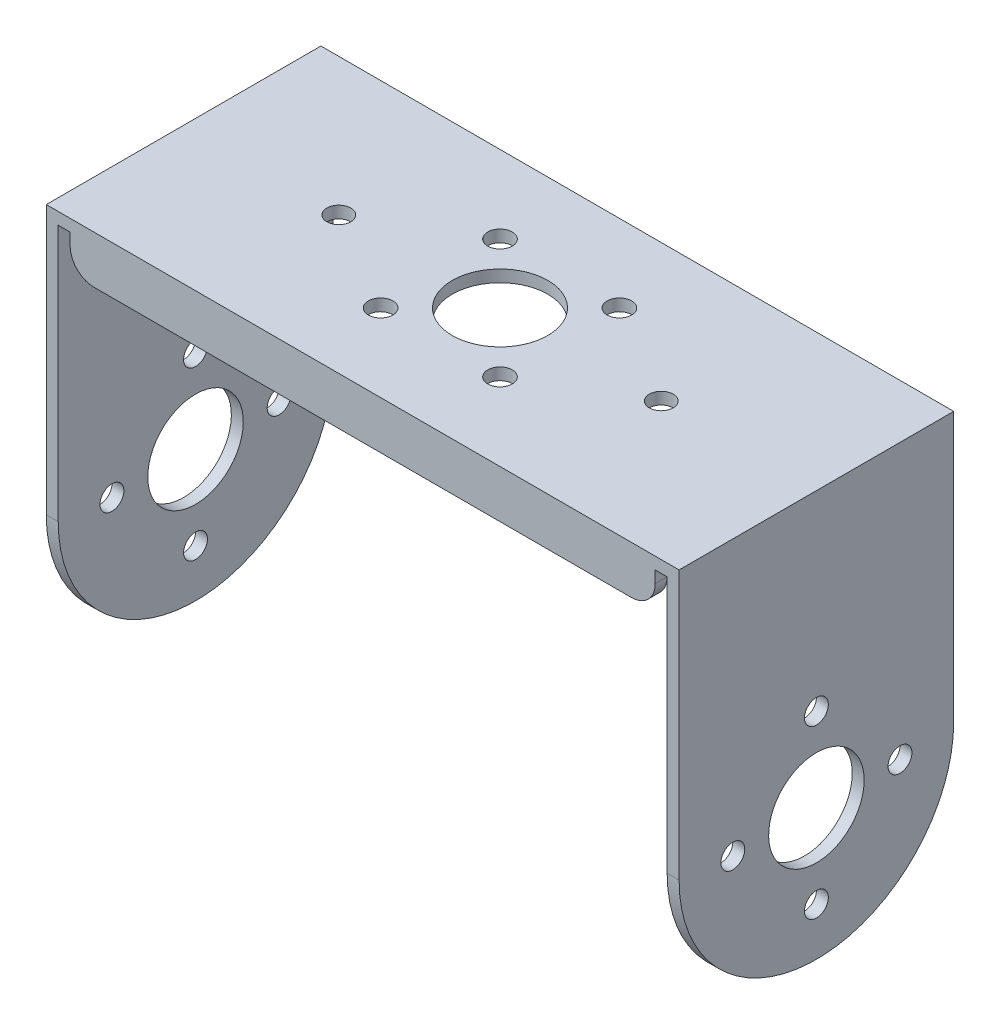
SolidWorks part; units mm, degrees
ref_plane "前视基准面" through (0, 0, 0) normal (0, 0, 1) x (1, 0, 0)
ref_plane "上视基准面" through (0, 0, 0) normal (0, 1, 0) x (1, 0, 0)
ref_plane "右视基准面" through (0, 0, 0) normal (1, 0, 0) x (0, 0, -1)
sketch "草图1" plane through (0, 0, 0) normal (0, 0, 1) x (1, 0, 0)
  line L0 (-26.5, 1) -> (-26.5, -32)
  line L1 (-26.5, -32) -> (-25.5, -32)
  line L2 (-25.5, -32) -> (-25.5, 0)
  line L3 (-25.5, 0) -> (25.5, 0)
  line L4 (25.5, 0) -> (25.5, -32)
  line L5 (25.5, -32) -> (26.5, -32)
  line L6 (26.5, -32) -> (26.5, 1)
  line L7 (26.5, 1) -> (-26.5, 1)
  dimension "D1" = 1
  dimension "D2" = 1
  dimension "D3" = 32
  dimension "D4" = 33
  dimension "D5" = 51
extrude "凸台-拉伸1" add sketch "草图1" along normal blind 21
sketch "草图2" plane through (-26.5, 0, 0) normal (-1, 0, 0) x (0, 0, 1)
  line L0 (10.5, -48.887) -> (10.5, 0.6402) construction
  line L1 (21, -32) -> (0, -32) construction
  line L5 (0, 1) -> (0, -32) construction
  line L6 (0, -32) -> (10.5, -32)
  line L7 (0, -32) -> (0, -21.5)
  arc A0 (0, -21.5) -> (10.5, -32) centre (10.5, -21.5) ccw
extrude "切除-拉伸1" cut sketch "草图2" against normal up to surface (53 mm away) up to face at (26.5, -15.5, 10.5)
ref_axis "基准轴1" through (-26.5, 1, 10.5) along (1, 0, 0)
ref_plane "基准面1" through (0, 0, 10.5) normal (0, 0, 1) x (1, 0, 0)
mirror "镜向1" about plane through (0, 0, 10.5) normal (0, 0, 1) of "切除-拉伸1"
sketch "草图3" plane through (26.5, 0, 0) normal (1, 0, 0) x (0, 0, -1)
  line L0 (-10.5, -38.5331) -> (-10.5, 10.5786) construction
  line L1 (-10.5, -32) -> (-2.4743, -32) construction
  line L2 (0, -21.5) -> (0, 1) construction
  circle A0 centre (-10.5, -22) radius 4
  circle A1 centre (-3.5, -22) radius 1
  circle A2 centre (-10.5, -15) radius 1
  circle A3 centre (-17.5, -22) radius 1
  circle A4 centre (-10.5, -29) radius 1
  arc A5 (-21, -21.5) -> (0, -21.5) centre (-10.5, -21.5) ccw construction
  dimension "D1" = 2
  dimension "D2" = 8
  dimension "D3" = 10
  dimension "D4" = 7
  dimension "D5" = 7
  dimension "D6" = 7
  dimension "D7" = 7
  dimension "D8" = 10.5
extrude "切除-拉伸2" cut sketch "草图3" against normal up to surface (53 mm away) up to face at (-26.5, -12.875, 10.5)
sketch "草图4" plane through (0, 1, 0) normal (0, 1, 0) x (1, 0, 0)
  line L0 (-29.1776, -10.5) -> (29.4412, -10.5) construction
  line L1 (0, 5.3481) -> (0, -30.3599) construction
  line L2 (26.5, -21) -> (-26.5, -21) construction
  line L3 (-26.5, -21) -> (-26.5, 0) construction
  line L4 (26.5, -21) -> (26.5, 0) construction
  circle A0 centre (0, -10.5) radius 4
  circle A1 centre (5, -5.5) radius 1.0266
  circle A2 centre (13.5, -10.5) radius 1
  circle A3 centre (-13.5, -10.5) radius 1
  circle A4 centre (5, -15.5) radius 1.0266
  circle A5 centre (-5, -5.5) radius 1.0266
  circle A6 centre (-5, -15.5) radius 1.0266
  dimension "D1" = 5
  dimension "D2" = 5
  dimension "D3" = 13.5
  dimension "D4" = 13.5
  dimension "D5" = 5
  dimension "D6" = 5
  dimension "D9" = 10
  dimension "D10" = 10
  dimension "D11" = 10
  dimension "D7" = 58.6188
  dimension "D8" = 10.5
  dimension "D12" = 26.5
  dimension "D13" = 26.5
extrude "切除-拉伸3" cut sketch "草图4" against normal blind 1
sketch "草图6" plane through (0, 0, 21) normal (0, 0, 1) x (1, 0, 0)
  line L0 (24.5, 0) -> (24.5, 1)
  line L1 (-25.5, 0) -> (25.5, 0) construction
  line L2 (26.5, 1) -> (-26.5, 1) construction
  line L3 (24.5, 1) -> (-24.5, 1)
  line L4 (-24.5, 1) -> (-24.5, 0)
  line L5 (-24.5, 0) -> (24.5, 0)
  line L6 (25.5, 0) -> (25.5, -21.5) construction
  line L7 (-25.5, -21.5) -> (-25.5, 0) construction
  dimension "D1" = 1
  dimension "D2" = 1
extrude "凸台-拉伸2" add sketch "草图6" along normal blind 1
sketch "草图7" plane through (0, 0, 0) normal (0, -1, 0) x (1, 0, 0)
  line L0 (24.5, 21) -> (24.5, 22)
  line L1 (24.5, 22) -> (-24.5, 22)
  line L2 (-24.5, 22) -> (-24.5, 21)
  line L3 (-24.5, 21) -> (24.5, 21)
extrude "凸台-拉伸3" add sketch "草图7" along normal blind 3
sketch "草图8" plane through (0, 0, 0) normal (0, -1, 0) x (1, 0, 0)
  line L0 (25.5, 21) -> (24.5, 21)
  line L1 (24.5, 21) -> (24.5, 22)
  arc A0 (24.5, 22) -> (25.5, 21) centre (25.5, 22) ccw
ref_plane "基准面2" through (0, 0, 0) normal (1, 0, 0) x (0, 0, -1)
fillet "圆角1" radius 2 2 edges at (-24.5, -3, 21.5) (24.5, -3, 21.5)
mirror "镜向3" about plane through (0, 0, 10.5) normal (0, 0, 1) of "凸台-拉伸3", "凸台-拉伸2", "圆角1"
sketch "草图9" plane through (26.5, 0, 0) normal (1, 0, 0) x (0, 0, -1)
  line L0 (-21, 1) -> (-22, 1)
  line L1 (-22, 1) -> (-22, -21.5)
  line L2 (0, 1) -> (1, 1)
  line L3 (1, 1) -> (1, -21.5)
  line L4 (-21, -21.5) -> (-21, 1) construction
  line L5 (-21, -21.5) -> (-21, 1)
  line L6 (0, -21.5) -> (0, 1) construction
  line L7 (0, -21.5) -> (0, 1)
  arc A0 (-21, -21.5) -> (0, -21.5) centre (-10.5, -21.5) ccw construction
  arc A1 (-21, -21.5) -> (0, -21.5) centre (-10.5, -21.5) ccw
  arc A2 (-22, -21.5) -> (1, -21.5) centre (-10.5, -21.5) ccw
extrude "凸台-拉伸4" add sketch "草图9" against normal blind 1
mirror "镜向4" about plane through (0, 0, 0) normal (1, 0, 0) of "凸台-拉伸4"
sketch "草图10" plane through (0, 1, 0) normal (0, 1, 0) x (1, 0, 0)
  line L1 (-25.5, 1) -> (-24.5, 1)
  line L2 (-25.5, 1) -> (-25.5, 0)
  line L3 (-25.5, 0) -> (-24.5, 0)
  line L4 (-24.5, 1) -> (-24.5, 0)
  line L5 (-25.5, -21) -> (-24.5, -21)
  line L6 (-25.5, -21) -> (-25.5, -22)
  line L7 (-25.5, -22) -> (-24.5, -22)
  line L8 (-24.5, -21) -> (-24.5, -22)
  line L9 (24.5, 1) -> (25.5, 1)
  line L10 (24.5, 1) -> (24.5, 0)
  line L11 (24.5, 0) -> (25.5, 0)
  line L12 (25.5, 1) -> (25.5, 0)
  line L13 (24.5, -21) -> (25.5, -21)
  line L14 (24.5, -21) -> (24.5, -22)
  line L15 (24.5, -22) -> (25.5, -22)
  line L16 (25.5, -21) -> (25.5, -22)
extrude "凸台-拉伸5" add sketch "草图10" against normal blind 1
